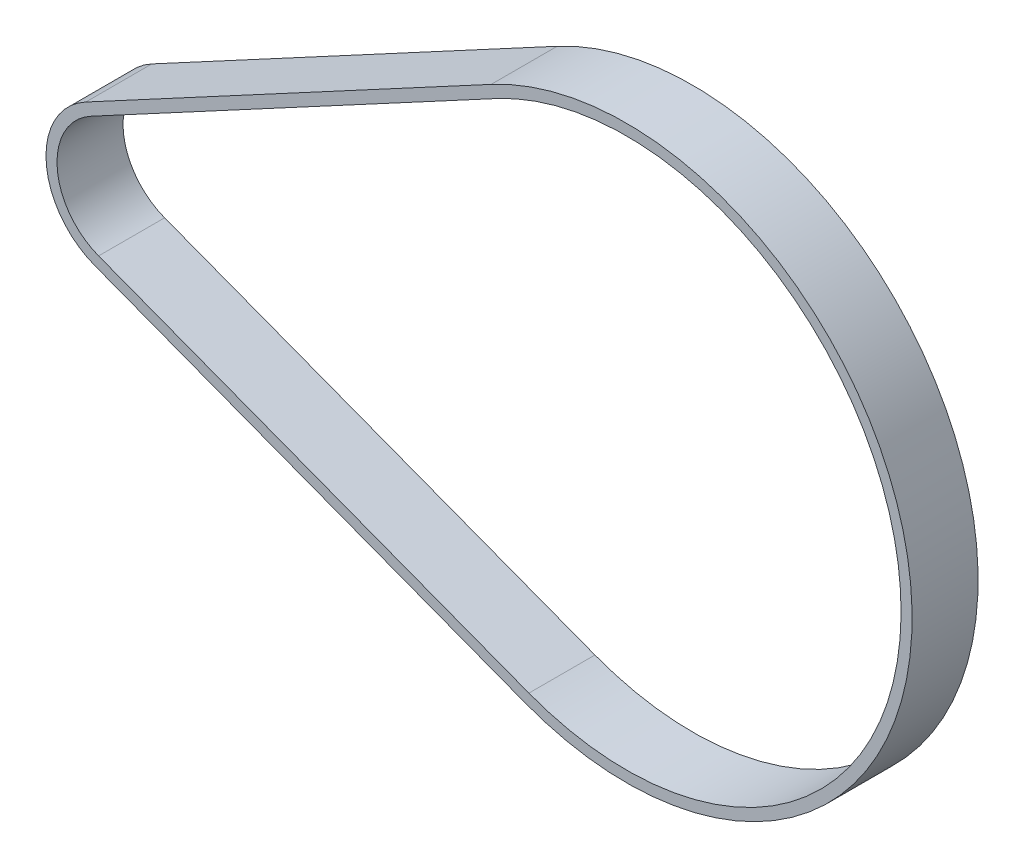
SolidWorks part; units mm, degrees
ref_plane "Front Plane" through (0, 0, 0) normal (0, 0, 1) x (1, 0, 0)
ref_plane "Top Plane" through (0, 0, 0) normal (0, 1, 0) x (1, 0, 0)
ref_plane "Right Plane" through (0, 0, 0) normal (1, 0, 0) x (0, 0, -1)
sketch "Sketch2" plane through (0, 0, 0) normal (0, 0, 1) x (1, 0, 0)
  line L0 (0, 0) -> (1, 0) construction
  line L1 (0, 0) -> (0, 1) construction
  line L4 (36.9486, -24.3097) -> (-2.1662, -9.4493)
  line L5 (-2.9201, 2.1066) -> (33.9323, 21.9232)
  arc A1 (33.9323, 21.9232) -> (36.9486, -24.3097) centre (45.9925, -0.5048) cw
  arc A2 (-2.1662, -9.4493) -> (-2.9201, 2.1066) centre (0.0943, -3.4993) cw
extrude "Extrude-Thin1" add sketch "Sketch2" against normal blind 6 from offset 1 thin offset against normal yes thin type mid plane wall 1
